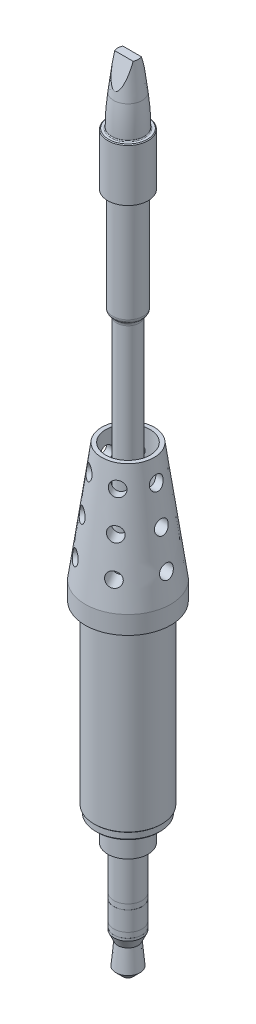
SolidWorks part; units mm, degrees
other "Jack Tip"
other "Jack Divider 2"
other "Jack Middle"
other "Jack Divider 1"
other "Jack Base"
other "Body"
other "Guard"
ref_plane "Front Plane" through (0, 0, 0) normal (0, 0, 1) x (1, 0, 0)
ref_plane "Top Plane" through (0, 0, 0) normal (0, 1, 0) x (1, 0, 0)
ref_plane "Right Plane" through (0, 0, 0) normal (1, 0, 0) x (0, 0, -1)
sketch "Sketch1" plane through (0, 0, 0) normal (0, 1, 0) x (1, 0, 0)
  circle A0 centre (0, 0) radius 4.2
  dimension "D1" = 8.4
extrude "Boss-Extrude1" add sketch "Sketch1" along normal blind 22
sketch "Sketch9" plane through (0, 22, 0) normal (0, 1, 0) x (1, 0, 0)
  circle A0 centre (0, 0) radius 3.4
  dimension "D1" = 6.8
extrude "Boss-Extrude8" add sketch "Sketch9" along normal blind 0.7
sketch "Sketch10" plane through (0, 22.7, 0) normal (0, 1, 0) x (1, 0, 0)
  circle A0 centre (0, 0) radius 3.75
  dimension "D1" = 7.5
extrude "Boss-Extrude9" add sketch "Sketch10" along normal blind 2.8
sketch "Sketch11" plane through (0, 25.5, 0) normal (0, 1, 0) x (1, 0, 0)
  circle A0 centre (0, 0) radius 1.8
  dimension "D1" = 3.6
extrude "Boss-Extrude10" add sketch "Sketch11" along normal blind 2.9
sketch "Sketch12" plane through (0, 28.4, 0) normal (0, 1, 0) x (1, 0, 0)
  circle A0 centre (0, 0) radius 1.4
  dimension "D1" = 2.8
extrude "Boss-Extrude11" add sketch "Sketch12" along normal blind 24.25
sketch "Sketch13" plane through (0, 52.65, 0) normal (0, 1, 0) x (1, 0, 0)
  circle A0 centre (0, 0) radius 1.9
  dimension "D1" = 3.8
extrude "Boss-Extrude12" add sketch "Sketch13" along normal blind 13.2
sketch "Sketch14" plane through (0, 65.85, 0) normal (0, 1, 0) x (1, 0, 0)
  circle A0 centre (0, 0) radius 2.5
  dimension "D1" = 5
extrude "Boss-Extrude13" add sketch "Sketch14" along normal blind 6.9
sketch "Sketch15" plane through (0, 0, 0) normal (1, 0, 0) x (0, 0, -1)
  line L0 (0, -927.2764) -> (0, 49072.7236) construction
  line L2 (-2, 72.75) -> (-2, 74.75)
  line L3 (2.5, 72.75) -> (-2.5, 72.75) construction
  line L4 (-2, 74.75) -> (-1.25, 80.75)
  line L5 (-1.25, 80.75) -> (0, 80.75)
  line L6 (0, 80.75) -> (0, 72.75)
  line L7 (0, 72.75) -> (-2, 72.75)
  dimension "D1" = 4
  dimension "D2" = 2.5
  dimension "D3" = 8
  dimension "D4" = 2
revolve "Revolve2" add sketch "Sketch15" angle 360 about L0
sketch "Sketch16" plane through (0, 0, 0) normal (1, 0, 0) x (0, 0, -1)
  line L0 (1.25, 80.75) -> (-1.25, 80.75) construction
  line L1 (2, 74.75) -> (-2, 74.75) construction
  line L3 (1.25, 80.75) -> (-1.25, 80.75) construction
  line L4 (-1.25, 80.75) -> (-2.1233, 74.75) construction
  line L5 (1.25, 80.75) -> (2, 74.75) construction
  line L6 (-0.5, 80.75) -> (0.5, 80.75)
  line L7 (0.5, 80.75) -> (1.65, 77.5504)
  line L8 (1.65, 77.5504) -> (1.25, 80.75)
  line L9 (1.25, 80.75) -> (0.5, 80.75)
  line L10 (0, 4.62) -> (0, -4.62) construction
  line L11 (-1.65, 77.5504) -> (-1.25, 80.75)
  line L12 (-0.5, 80.75) -> (-1.65, 77.5504)
  line L13 (-1.25, 80.75) -> (-0.5, 80.75)
  point P7 (0, 80.75)
  dimension "D2" = 1
  dimension "D3" = 3.4
extrude "Cut-Extrude1" cut sketch "Sketch16" against normal through all both and the other way through all contours L13 L11 L12 | L8 L9 L7 region at (0, 79.6835, -1.1333) region at (0, 79.6835, 1.1333)
fillet "Fillet1" radius 30 1 edges at (0, 74.75, -2)
chamfer "Chamfer1" distance 0.1 angle 45 2 edges at (0, 0, 4.2) (0, 72.75, 2.5)
chamfer "Chamfer2" distance 0.4 angle 45 2 edges at (0, 25.5, 3.75) (0, 22.7, 3.75)
chamfer "Chamfer3" distance 0.6 angle 30 1 edges at (0, 65.85, 2.5) first distance on face at (0, 65.85, 1.9)
fillet "Fillet3" radius 0.1 1 edges at (0, 72.75, -2)
chamfer "Chamfer4" distance 0.6 angle 45 1 edges at (0, 52.65, 1.9)
fillet "Fillet4" radius 0.6 2 edges at (0, 52.75, 1.4) (0, 53.25, 1.9)
sketch "Sketch2" plane through (0, 0, 0) normal (0, -1, 0) x (1, 0, 0)
  circle A0 centre (0, 0) radius 4
  dimension "D1" = 8
extrude "Boss-Extrude2" add sketch "Sketch2" along normal blind 1 separate body
sketch "Sketch3" plane through (0, -1, 0) normal (0, -1, 0) x (1, 0, 0)
  circle A0 centre (0, 0) radius 2.5
  dimension "D1" = 5
extrude "Boss-Extrude3" add sketch "Sketch3" along normal blind 3
sketch "Sketch4" plane through (0, -4, 0) normal (0, -1, 0) x (1, 0, 0)
  circle A0 centre (0, 0) radius 1.75
  dimension "D1" = 3.5
extrude "Boss-Extrude4" add sketch "Sketch4" along normal blind 5.35
sketch "Sketch5" plane through (0, -9.35, 0) normal (0, -1, 0) x (1, 0, 0)
  circle A2 centre (0, 0) radius 1.74
  circle A3 centre (0, 0) radius 1.74
  dimension "D1" = 0.01
extrude "Boss-Extrude5" add sketch "Sketch5" along normal blind 0.65 separate body
sketch "Sketch6" plane through (0, -10, 0) normal (0, -1, 0) x (1, 0, 0)
  circle A0 centre (0, 0) radius 1.75 construction
  circle A1 centre (0, 0) radius 1.75
extrude "Boss-Extrude6" add sketch "Sketch6" along normal blind 2.4 separate body
sketch "Sketch7" plane through (0, -12.4, 0) normal (0, -1, 0) x (1, 0, 0)
  circle A2 centre (0, 0) radius 1.74
  circle A3 centre (0, 0) radius 1.74
  dimension "D1" = 0.01
extrude "Boss-Extrude7" add sketch "Sketch7" along normal blind 0.65 separate body
sketch "Sketch8" plane through (0, 0, 0) normal (1, 0, 0) x (0, 0, -1)
  line L0 (0, -1013.0181) -> (0, 48986.9819) construction
  line L2 (0, -13.05) -> (-1.75, -13.05)
  line L3 (-1.74, -13.05) -> (1.74, -13.05) construction
  line L4 (-1.75, -13.05) -> (-1.75, -13.35)
  line L5 (-1.75, -13.35) -> (-1.25, -14.4362)
  line L6 (-1.25, -14.4362) -> (-1.5, -17.225)
  line L7 (-1.5, -17.225) -> (-0.625, -18.1)
  line L8 (-0.625, -18.1) -> (0, -18.1)
  line L9 (0, -18.1) -> (0, -13.05)
  line L10 (-4, -1) -> (4, -1) construction
  point P12 (-0.3125, -18.1)
  dimension "D1" = 3.5
  dimension "D2" = 3
  dimension "D3" = 1.25
  dimension "D4" = 17.1
  dimension "D5" = 2.5
  dimension "D6" = 0.3
  dimension "D7" = 2.8
  dimension "D8" = 45
revolve "Revolve1" add sketch "Sketch8" angle 360 about L0
chamfer "Chamfer5" distance 0.2 angle 45 1 edges at (0, -1, -4)
sketch "Sketch17" plane through (0, 22, 0) normal (0, 1, 0) x (1, 0, 0)
  circle A0 centre (0, 0) radius 5.3
  dimension "D1" = 10.6
extrude "Boss-Extrude14" add sketch "Sketch17" along normal blind 2.25 separate body
sketch "Sketch18" plane through (0, 0, 0) normal (1, 0, 0) x (0, 0, -1)
  line L0 (-5.3, 24.25) -> (-3.25, 39)
  line L1 (-3.25, 39) -> (0, 39)
  line L2 (0, 5.83) -> (0, -5.83) construction
  line L3 (0, 39) -> (0, 24.25)
  line L4 (5.3, 24.25) -> (-5.3, 24.25) construction
  line L5 (0, 24.25) -> (-5.3, 24.25)
  line L6 (4.2, 22) -> (-4.2, 22) construction
  line L7 (0, -958.0782) -> (0, 49041.9218) construction
  dimension "D1" = 17
  dimension "D2" = 6.5
revolve "Revolve3" add sketch "Sketch18" angle 360 about L7
sketch "Sketch19" plane through (0, 39, 0) normal (0, 1, 0) x (1, 0, 0)
  circle A2 centre (0, 0) radius 2.75
  circle A3 centre (0, 0) radius 2.75
  dimension "D1" = 0.5
extrude "Cut-Extrude2" cut sketch "Sketch19" against normal through all
sketch "Sketch20" plane through (0, 22, 0) normal (0, -1, 0) x (1, 0, 0)
  circle A0 centre (0, 0) radius 3.8
  dimension "D1" = 7.6
extrude "Cut-Extrude4" cut sketch "Sketch20" against normal blind 3.8
fillet "Chamfer6" radius 0.4 1 edges at (0, 22, -3.8) type face fillet profile chamfer first side face at (0, 25.8, -3.8) second side face at (0, 22, -3.8)
sketch "Sketch21" plane through (0, 0, 0) normal (1, 0, 0) x (0, 0, -1)
  line L0 (0, 39) -> (0, 24.25) construction
  line L1 (3.25, 39) -> (-3.25, 39) construction
  line L2 (0, 5.83) -> (0, -5.83) construction
  line L3 (-5.3, 24.25) -> (5.3, 24.25) construction
  line L4 (0, 36.45) -> (0, 32) construction
  circle A0 centre (0, 36.45) radius 0.85
  circle A1 centre (0, 32) radius 0.85
  circle A2 centre (0, 27.55) radius 0.85
  dimension "D1" = 1.7
  dimension "D2" = 2.55
  dimension "D4" = 4.45
  dimension "D3" = 3
extrude "Cut-Extrude6" cut sketch "Sketch21" against normal through all both and the other way through all
pattern_circular "CirPattern1" count 3 over 360 about axis through (0, 39, 0) along (0, 1, 0) of "Cut-Extrude6" reverse direction yes
ref_axis "Axis1" through (0, 22, 0) along (0, -1, 0)
